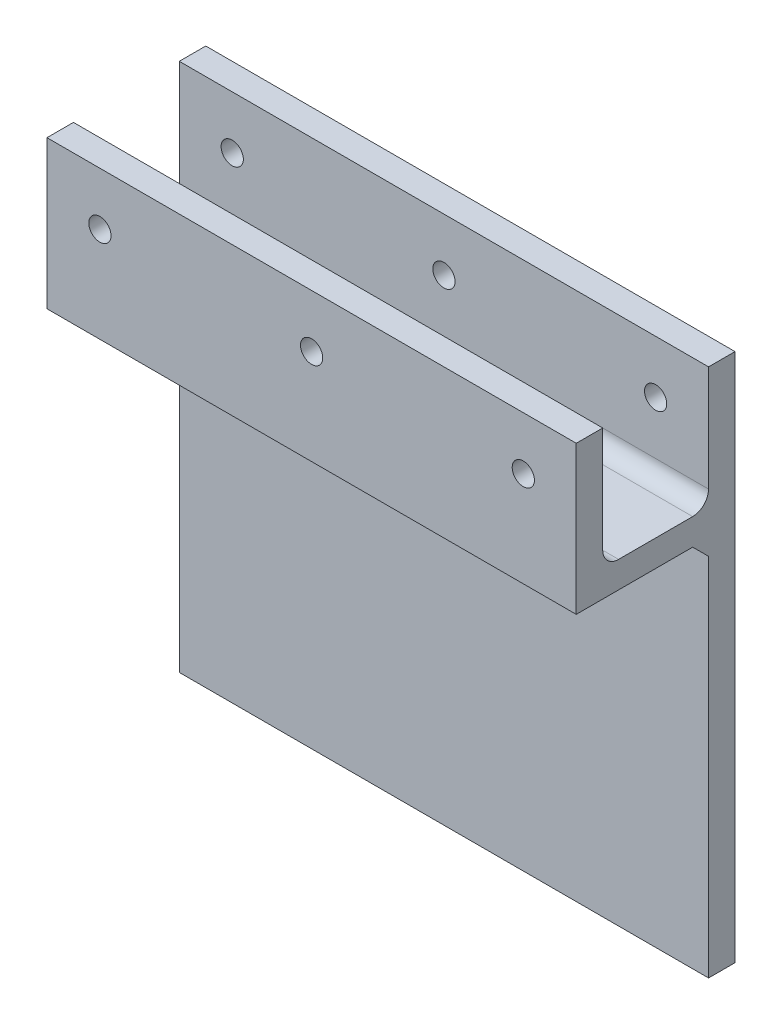
SolidWorks part; units mm, degrees
ref_plane "前视基准面" through (0, 0, 0) normal (0, 0, 1) x (1, 0, 0)
ref_plane "上视基准面" through (0, 0, 0) normal (0, 1, 0) x (1, 0, 0)
ref_plane "右视基准面" through (0, 0, 0) normal (1, 0, 0) x (0, 0, -1)
sketch "草图1" plane through (0, 0, 0) normal (0, 0, 1) x (1, 0, 0)
  line L1 (-50, 50) -> (50, 50)
  line L2 (-50, 50) -> (-50, -50)
  line L3 (-50, -50) -> (50, -50)
  line L4 (50, 50) -> (50, -50)
  line L5 (-50, 50) -> (50, -50) construction
  line L6 (-50, -50) -> (50, 50) construction
  line L7 (-50, 27) -> (50, 27)
  line L8 (-50, 27) -> (-50, 22)
  line L9 (-50, 22) -> (50, 22)
  line L10 (50, 27) -> (50, 22)
  line L11 (-50, 27) -> (50, 22) construction
  line L12 (-50, 22) -> (50, 27) construction
  point P0 (0, 0)
  point P5 (0, 24.5)
  dimension "D1" = 100
  dimension "D2" = 100
  dimension "D3" = 5
  dimension "D4" = 23
extrude "凸台-拉伸1" add sketch "草图1" along normal blind 5 contours L9 L2 L3 L4 | L2 L7 L4 L1 region at (0, 38.5, 0) region at (0, -14, 0)
extrude "凸台-拉伸2" add sketch "草图1<3>" along normal blind 30 contours L2 L9 L4 L7 region at (0, 24.5, 0)
sketch "草图1<3>" plane through (0, 0, 0) normal (0, 0, 1) x (1, 0, 0) same geometry as "草图1"
sketch "草图2" plane through (0, 27, 0) normal (0, 1, 0) x (1, 0, 0)
  line L0 (-50, -30) -> (-50, -5) construction
  line L1 (-50, -25) -> (50, -25)
  line L2 (-50, -25) -> (-50, -30)
  line L3 (-50, -30) -> (50, -30)
  line L4 (50, -25) -> (50, -30)
  line L5 (-50, -25) -> (50, -30) construction
  line L6 (-50, -30) -> (50, -25) construction
  point P0 (0, -27.5)
  dimension "D1" = 5
extrude "凸台-拉伸3" add sketch "草图2" along normal blind 23
sketch "草图3" plane through (0, 0, 30) normal (0, 0, 1) x (1, 0, 0)
  line L0 (-50, 50) -> (-50, 22) construction
  line L1 (-50, 50) -> (50, 50) construction
  circle A0 centre (-40, 40) radius 2.1
  circle A1 centre (0, 40) radius 2.1
  circle A2 centre (40, 40) radius 2.1
  dimension "D1" = 10
  dimension "D3" = 4.2
  dimension "D2" = 10
  dimension "D5" = 40
  dimension "D4" = 3
extrude "切除-拉伸1" cut sketch "草图3" against normal through all
fillet "圆角1" radius 3 2 edges at (0, 27, 25) (0, 27, 5)
sketch "草图8" plane through (-50, 0, 0) normal (-1, 0, 0) x (0, 0, 1)
  line L0 (5, 19) -> (8, 22)
  line L1 (5, 22) -> (5, -50) construction
  line L2 (30, 22) -> (5, 22) construction
  line L3 (8, 22) -> (5, 22)
  line L4 (5, 22) -> (5, 19)
  dimension "D1" = 3
  dimension "D2" = 3
extrude "凸台-拉伸4" add sketch "草图8" against normal through all
